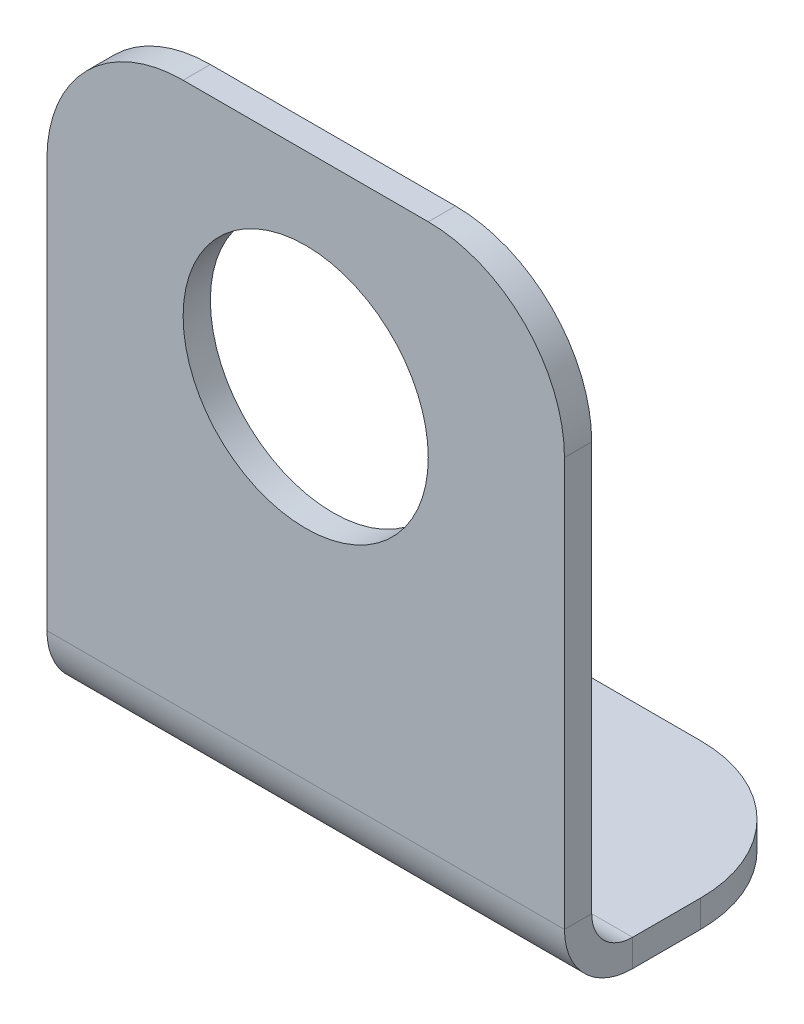
SolidWorks part; units mm, degrees
note: The reader was unsure of these and kept them because the rebuilt part matched: thickness of "基体-法兰1", "边线-法兰1", "钣金6", "钣金7"; flange length of "边线-法兰1".
material "Q355"
ref_plane "前视基准面" through (0, 0, 0) normal (0, 0, 1) x (1, 0, 0)
ref_plane "上视基准面" through (0, 0, 0) normal (0, 1, 0) x (1, 0, 0)
ref_plane "右视基准面" through (0, 0, 0) normal (1, 0, 0) x (0, 0, -1)
sketch "草图1" plane through (0, 0, 0) normal (0, 0, 1) x (1, 0, 0)
  line L0 (-19, 15) -> (-19, -25)
  line L3 (-19, -25) -> (19, -25)
  line L4 (19, -25) -> (19, 15)
  line L5 (-19, 15) -> (19, 15)
  circle A2 centre (0, 0) radius 9
  dimension "D1" = 18
  dimension "D2" = 38
  dimension "D3" = 19
  dimension "D4" = 25
  dimension "D5" = 40
base flange "基体-法兰1" sketch "草图1" thickness 2 reverse thickness direction no parameters "D1"=3
edge flange "边线-法兰1" sketch "草图14" flange angle 90 flange length 20 flange position bend outside bend radius 3 thickness 2 relief rectangular parameters "D6"=10
sketch "草图14" plane through (0, -25, -2) normal (0, -1, 0) x (-1, 0, 0)
  line L0 (19, 0) -> (-19, 0) construction
  line L1 (19, 0) -> (-19, 0)
  line L2 (-19, 0) -> (-19, 18)
  line L3 (-19, 18) -> (19, 18)
  line L4 (19, 18) -> (19, 0)
bend "边线折弯1" bend radius 3 bend angle 90 parameters "D5"=1
fillet "圆角1" radius 10 4 edges at (-19, -29, -20) (19, -29, -20) (19, 15, -1) (-19, 15, -1)
sketch "折弯-线1" [suppressed] plane through (0, 0, 0) normal (0, 1, 0) x (1, 0, 0)
sketch "边界框1" [suppressed] plane through (0, 0, 0) normal (0, 1, 0) x (1, 0, 0)
sheet metal parameters "钣金6" thickness 2 parameters "D1"=8, "D7"=3
flat pattern "平板型式6" [suppressed]
sketch "折弯-线2" plane through (0, 0, 0) normal (0, 1, 0) x (1, 0, 0)
sketch "边界框2" [suppressed] plane through (0, 0, 0) normal (0, 1, 0) x (1, 0, 0)
sheet metal parameters "钣金7" thickness 2 parameters "D1"=8, "D7"=3
flat pattern "平板型式6"
sketch "折弯-线2" plane through (0, 0, 0) normal (0, 0, 1) x (1, 0, 0)
  line L0 (-19, -28.1416) -> (19, -28.1416) construction
  line L1 (-19, -28.1416) -> (19, -28.1416) construction
sketch3d "边界框2" [suppressed]
  line L0 (19, 15, 0) -> (19, -46.2832, 0) construction
  line L1 (-19, 15, 0) -> (-19, -46.2832, 0) construction
  line L2 (19, 15, 0) -> (-19, 15, 0) construction
  line L3 (19, -46.2832, 0) -> (-19, -46.2832, 0) construction
bend of the flat pattern "展开-<边线折弯1>1"
